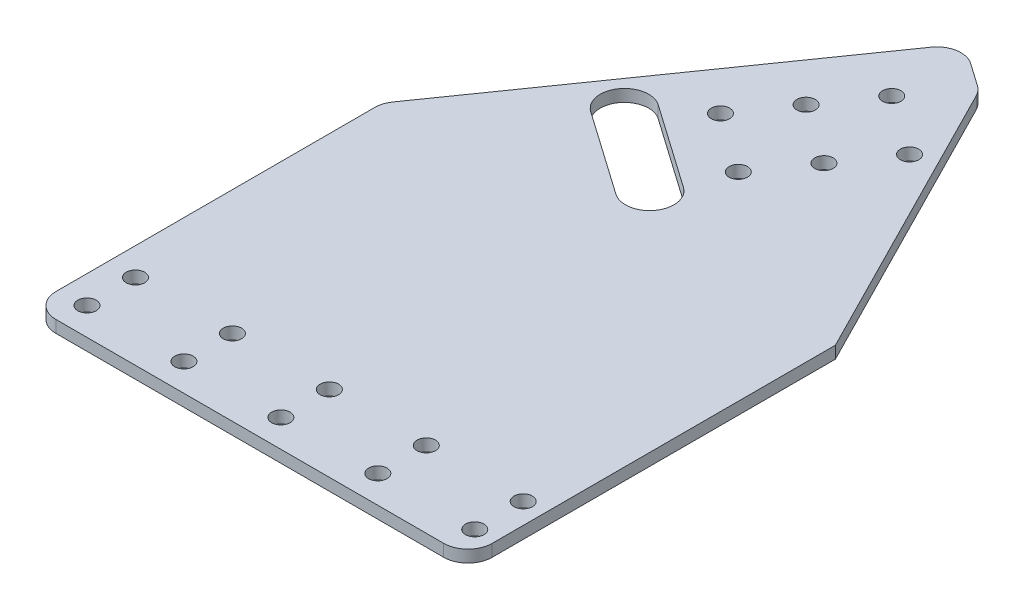
SolidWorks part; units mm, degrees
material "6061-T6 (SS)"
ref_plane "Front Plane" through (0, 0, 0) normal (0, 0, 1) x (1, 0, 0)
ref_plane "Top Plane" through (0, 0, 0) normal (0, 1, 0) x (1, 0, 0)
ref_plane "Right Plane" through (0, 0, 0) normal (1, 0, 0) x (0, 0, -1)
sketch "Sketch1" plane through (0, 0, 0) normal (0, 1, 0) x (1, 0, 0)
  line L5 (0, 0) -> (114.3, 0)
  line L6 (0, 0) -> (0, 181.61)
  line L7 (0, 181.61) -> (114.3, 181.61)
  line L8 (114.3, 0) -> (114.3, 181.61)
  dimension "D1" = 181.61
  dimension "D2" = 114.3
extrude "Boss-Extrude1" add sketch "Sketch1" along normal blind 3.175
sketch "Sketch2" plane through (0, 3.175, 0) normal (0, 1, 0) x (1, 0, 0)
  line L0 (0, 0) -> (114.3, 0) construction
  line L1 (0, 181.61) -> (0, 0) construction
  circle A0 centre (7.239, 7.239) radius 2.413
  circle A2 centre (7.239, 19.939) radius 2.413
  circle A3 centre (32.639, 19.939) radius 2.413
  circle A4 centre (58.039, 19.939) radius 2.413
  circle A5 centre (83.439, 19.939) radius 2.413
  circle A6 centre (108.839, 19.939) radius 2.413
  circle A7 centre (32.639, 7.239) radius 2.413
  circle A8 centre (58.039, 7.239) radius 2.413
  circle A9 centre (83.439, 7.239) radius 2.413
  circle A10 centre (108.839, 7.239) radius 2.413
  dimension "D1" = 4.826
  dimension "D2" = 7.239
  dimension "D3" = 7.239
  dimension "D4" = 2
  dimension "D5" = 5
extrude "Cut-Extrude1" cut sketch "Sketch2" against normal through all
sketch "Sketch4" plane through (0, 0, 0) normal (0, -1, 0) x (1, 0, 0)
  line L0 (62.8285, -181.61) -> (0, -91.8816)
  line L1 (114.3, -181.61) -> (0, -181.61) construction
  line L2 (62.8285, -181.61) -> (0, -181.61)
  line L3 (0, -181.61) -> (0, -91.8816)
  line L4 (62.8285, -181.61) -> (114.3, -145.5693)
  line L6 (114.3, 0) -> (114.3, -181.61) construction
  line L7 (114.3, -145.5693) -> (114.3, -181.61)
  line L8 (114.3, -181.61) -> (62.8285, -181.61)
  line M20 (0, 0) -> (0, -181.61)
  line M21 (0, -181.61) -> (114.3, -181.61)
  line M22 (114.3, -181.61) -> (114.3, 0)
  dimension "D1" = 35
  dimension "D3" = 89.7284
extrude "Cut-Extrude3" cut sketch "Sketch4" against normal through all contours L4 M21 M22 | L0 M21 M20 region at (20.9428, 0, -151.7005) region at (97.1428, 0, -169.5964)
sketch "Sketch5" plane through (0, 0, 0) normal (0, -1, 0) x (1, 0, 0)
  line L0 (75.3992, -172.8079) -> (114.3, -96.2796)
  line L1 (62.8285, -181.61) -> (114.3, -145.5693) construction
  line L3 (75.3992, -172.8079) -> (114.3, -145.5693)
  line L4 (114.3, -145.5693) -> (114.3, -96.2796)
extrude "Cut-Extrude4" cut sketch "Sketch5" against normal through all
sketch "Sketch3" plane through (0, 0, 0) normal (0, -1, 0) x (1, 0, 0)
  line L0 (65.1315, -160.2039) -> (44.1348, -130.2176) construction
  line L1 (65.1315, -160.2039) -> (87.4419, -144.582) construction
  line L2 (44.1348, -130.2176) -> (66.4452, -114.5957) construction
  line L3 (87.4419, -144.582) -> (66.4452, -114.5957) construction
  line L4 (0, -91.8816) -> (0, 0) construction
  circle A0 centre (65.1315, -160.2039) radius 2.413
  circle A6 centre (55.8894, -147.0049) radius 2.413
  circle A7 centre (46.6473, -133.8058) radius 2.413
  circle A8 centre (71.4943, -136.0782) radius 2.413
  circle A9 centre (62.2522, -122.8792) radius 2.413
  circle A10 centre (80.7363, -149.2773) radius 2.413
  point P7 (76.0526, -194.6865)
  point P8 (63.4595, -179.3372)
  point P9 (62.3915, -171.3464)
  point P20 (65.1315, -160.2039)
  point P21 (62.9271, -122.4067)
  dimension "D4" = 4.826
  dimension "D5" = 19.05
  dimension "D1" = 35
  dimension "D3" = 3
  dimension "D2" = 2
extrude "Cut-Extrude2" cut sketch "Sketch3" against normal through all
sketch "Sketch6" plane through (0, 0, 0) normal (0, -1, 0) x (1, 0, 0)
  line L0 (54.9446, -106.9739) -> (32.8898, -122.4169) construction
  line L1 (58.5868, -112.1756) -> (36.532, -127.6185)
  line L2 (51.3024, -101.7723) -> (29.2476, -117.2153)
  line L3 (62.8285, -181.61) -> (0, -91.8816) construction
  line L4 (62.8285, -181.61) -> (75.3992, -172.8079) construction
  arc A0 (58.5868, -112.1756) -> (51.3024, -101.7723) centre (54.9446, -106.9739) ccw
  arc A1 (29.2476, -117.2153) -> (36.532, -127.6185) centre (32.8898, -122.4169) ccw
  point P2 (43.9172, -114.6954)
  dimension "D1" = 26.924
  dimension "D2" = 12.7
  dimension "D3" = 9.4274
  dimension "D4" = 65.6603
extrude "Cut-Extrude5" cut sketch "Sketch6" against normal through all
fillet "Fillet1" radius 6.35 5 edges at (0, 1.5875, -91.8816) (75.3992, 1.5875, -172.8079) (62.8285, 1.5875, -181.61) (0, 1.5875, 0) (114.3, 1.5875, 0)
